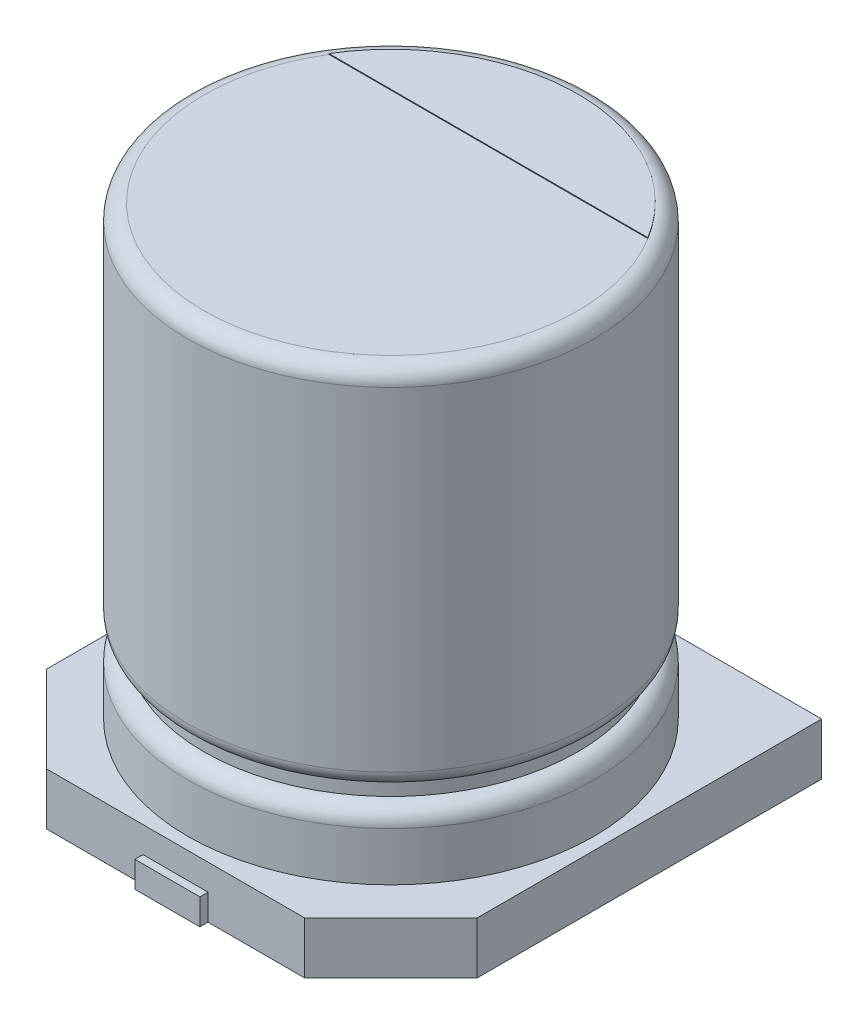
SolidWorks part; units mm, degrees
ref_plane "Front" through (0, 0, 0) normal (0, 0, 1) x (1, 0, 0)
ref_plane "Top" through (0, 0, 0) normal (0, 1, 0) x (1, 0, 0)
ref_plane "Right" through (0, 0, 0) normal (1, 0, 0) x (0, 0, -1)
sketch "Sketch1" plane through (0, 0, 0) normal (0, 0, 1) x (1, 0, 0)
  line L0 (0, 8.0822) -> (0, 0) construction
  line L1 (0, 5.5) -> (-2.3, 5.5)
  line L2 (-2.5, 5.3) -> (-2.5, 1.2)
  line L3 (-2.3, 1) -> (-2.3, 0.8)
  line L4 (-2.5, 0.6) -> (-2.5, 0)
  line L5 (-2.5, 0) -> (0, 0)
  line L6 (0, 0) -> (0, 5.5)
  line L7 (0, 0) -> (2.8151, 0) construction
  arc A0 (-2.3, 5.5) -> (-2.5, 5.3) centre (-2.3, 5.3) ccw
  arc A1 (-2.5, 1.2) -> (-2.3, 1) centre (-2.3, 1.2) ccw
  arc A2 (-2.3, 0.8) -> (-2.5, 0.6) centre (-2.3, 0.6) ccw
  dimension "D2" = 0.6
  dimension "D3" = 0.2
  dimension "D6" = 0.2
  dimension "D1" = 5
  dimension "D4" = 0.2
  dimension "D5" = 5.5
revolve "Revolve1" add sketch "Sketch1" angle 360 about L0
sketch "Sketch2" plane through (0, 5.5, 0) normal (0, 1, 0) x (1, 0, 0)
  line L0 (0, 0) -> (0, 2.3) construction
  line L1 (-1.9621, 1.2) -> (1.9621, 1.2)
  circle A0 centre (0, 0) radius 2.3 construction
  arc A1 (1.9621, 1.2) -> (-1.9621, 1.2) centre (0, 0) ccw
  dimension "D1" = 1.1
extrude "Boss-Extrude1" add sketch "Sketch2" along normal blind 0.01
sketch "Sketch3" plane through (0, 0, 0) normal (0, -1, 0) x (-1, 0, 0)
  line L0 (0, 0.5) -> (0, 0) construction
  line L1 (0, 0) -> (0.9284, 0) construction
  line L28 (1.5893, -2.65) -> (2.65, -1.5893)
  line L29 (2.65, -1.5893) -> (2.65, 2.65)
  line L31 (0.4, 2.65) -> (0.4, 0.5)
  line L32 (0.4, 0.5) -> (-0.4, 0.5)
  line L33 (-0.4, 0.5) -> (-0.4, 2.65)
  line L34 (2.65, 2.65) -> (-2.65, 2.65)
  line L35 (-2.65, 2.65) -> (-2.65, -1.5893)
  line L36 (-2.65, -1.5893) -> (-1.5893, -2.65)
  line L37 (-1.5893, -2.65) -> (1.5893, -2.65)
  line L38 (-0.4, -2.65) -> (-0.4, -0.5)
  line L39 (-0.4, -0.5) -> (0.4, -0.5)
  line L40 (0.4, -0.5) -> (0.4, -2.65)
  circle M43 centre (0, 0) radius 2.5
  dimension "D1" = 1
  dimension "D2" = 5.3
  dimension "D3" = 5.3
  dimension "D4" = 0.8
  dimension "D5" = 1.5
  dimension "D6" = 45
extrude "Boss-Extrude2" add sketch "Sketch3" along normal blind 0.64 contours L34 L35 L36 L37 L28 L29
extrude "Cut-Extrude1" cut sketch "Sketch3<3>" against normal blind 0.32 from vertex contours L33 L32 L31 M43 | L40 L39 L38 M43 | L31 L34 L33 M43 | L40 L38 L37 M43 region at (0, 0, 2.5694) region at (0, 0, 1.4947) region at (0, 0, -2.5694) region at (0, 0, -1.4947) starting at point (-2.65, -0.64, -2.65)
sketch "Sketch3<3>" plane through (0, 0, 0) normal (0, -1, 0) x (-1, 0, 0) same geometry as "Sketch3"
sketch "Sketch4" plane through (0, -0.32, 0) normal (0, -1, 0) x (1, 0, 0)
  line L0 (0.4, -0.5) -> (0.4, -2.65) construction
  line L1 (-0.4, -0.5) -> (0.4, -0.5)
  line L2 (-0.4, -0.5) -> (-0.4, -2.75)
  line L3 (-0.4, -2.75) -> (0.4, -2.75)
  line L4 (0.4, -0.5) -> (0.4, -2.75)
  line L5 (0, 0) -> (4.1796, 0) construction
  line L6 (-0.4, 0.5) -> (-0.4, 2.75)
  line L7 (-0.4, 0.5) -> (0.4, 0.5)
  line L8 (0.4, 0.5) -> (0.4, 2.75)
  line L9 (-0.4, 2.75) -> (0.4, 2.75)
  dimension "D1" = 2.25
extrude "Boss-Extrude3" add sketch "Sketch4" along normal blind 0.32
split line "Split Line1"
sketch "Sketch4<2>" plane through (0, -0.32, 0) normal (0, -1, 0) x (1, 0, 0) same geometry as "Sketch4"
